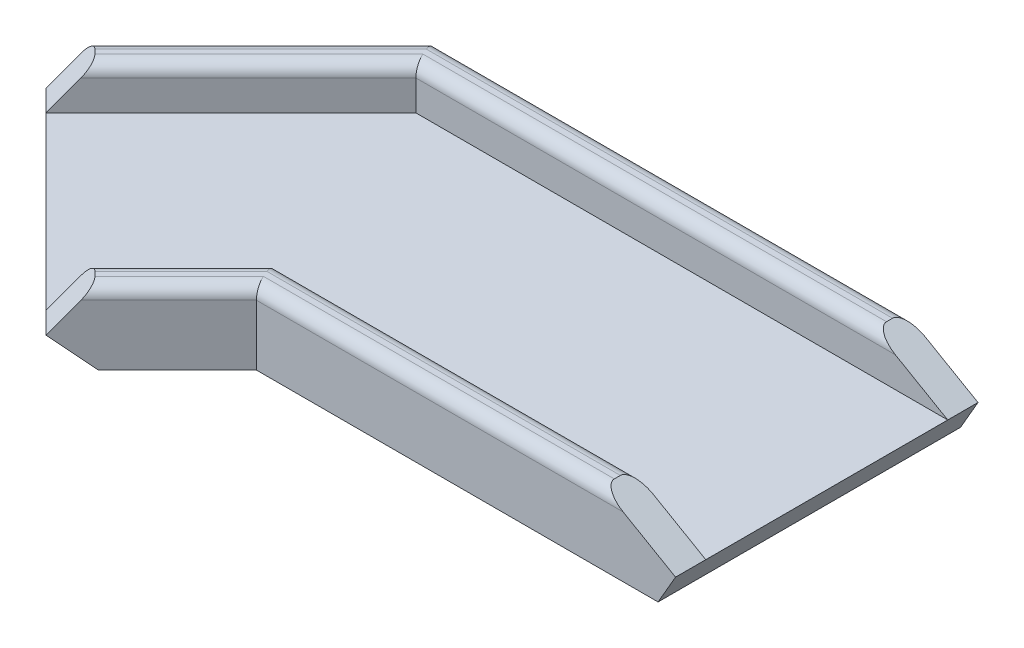
SolidWorks part; units mm, degrees
material "Maple"
ref_plane "Front Plane" through (0, 0, 0) normal (0, 0, 1) x (1, 0, 0)
ref_plane "Top Plane" through (0, 0, 0) normal (0, 1, 0) x (1, 0, 0)
ref_plane "Right Plane" through (0, 0, 0) normal (1, 0, 0) x (0, 0, -1)
sketch "Sketch1" plane through (0, 0, 0) normal (0, 0, 1) x (1, 0, 0)
  line L2 (-57.15, 3.175) -> (57.15, 3.175)
  line L3 (-57.15, 3.175) -> (-57.15, -3.175)
  line L4 (-57.15, -3.175) -> (57.15, -3.175)
  line L5 (57.15, 3.175) -> (57.15, -3.175)
  line L6 (-57.15, 3.175) -> (57.15, -3.175) construction
  line L7 (-57.15, -3.175) -> (57.15, 3.175) construction
  point P1 (0, 0)
  dimension "D1" = 6.35
  dimension "D2" = 114.3
extrude "Boss-Extrude1" add sketch "Sketch1" against normal blind 63.5 contours L5 L2 L4 region at (0, 0, 0)
sketch "Sketch2" plane through (0, 3.175, 0) normal (0, 1, 0) x (1, 0, 0)
  line L1 (57.15, 63.5) -> (-57.15, 63.5)
  line L2 (57.15, 63.5) -> (57.15, 57.15)
  line L3 (57.15, 57.15) -> (-57.15, 57.15)
  line L4 (-57.15, 63.5) -> (-57.15, 57.15)
  line L5 (57.15, 63.5) -> (57.15, 0) construction
  line L6 (-57.15, 0) -> (57.15, 0)
  line L7 (-57.15, 0) -> (-57.15, 6.35)
  line L8 (-57.15, 6.35) -> (57.15, 6.35)
  line L9 (57.15, 0) -> (57.15, 6.35)
  line L10 (-57.15, 63.5) -> (-57.15, 0) construction
  line L11 (-57.15, 0) -> (57.15, 0) construction
  dimension "D1" = 6.35
  dimension "D2" = 6.35
extrude "Boss-Extrude2" add sketch "Sketch2" along normal blind 8.89
sketch "Sketch3" plane through (0, 0, 0) normal (0, 0, 1) x (1, 0, 0)
  line L0 (57.15, 3.175) -> (41.7521, 12.065)
  line L1 (-57.15, 12.065) -> (57.15, 12.065) construction
  line L2 (41.7521, 12.065) -> (48.5274, 23.8003)
  line L3 (48.5274, 23.8003) -> (66.675, 13.3228)
  line L4 (66.675, 13.3228) -> (57.15, -3.175)
  line L5 (-57.15, -3.175) -> (57.15, -3.175) construction
  line L6 (57.15, 3.175) -> (53.4838, -3.175)
  line L7 (-57.15, -3.175) -> (57.15, -3.175) construction
  line L8 (53.4838, -3.175) -> (56.2335, -4.7625)
  line L9 (57.15, 3.175) -> (-57.15, 3.175) construction
  line L10 (56.2335, -4.7625) -> (57.15, -3.175)
  line L11 (57.15, 3.175) -> (-57.15, 3.175) construction
  point P13 (69.85, 18.822)
  point P15 (0, 0)
  point P18 (57.0096, 3.175)
  dimension "D1" = 30
  dimension "D2" = 19.05
extrude "Cut-Extrude1" cut sketch "Sketch3" against normal through all
sketch "Sketch5" plane through (0, 0, 0) normal (0, 1, 0) x (1, 0, 0)
  line L0 (-57.15, 63.5) -> (-30.8474, 0)
  line L2 (-30.8474, 0) -> (-57.15, 0)
  line L3 (-57.15, 0) -> (-57.15, 63.5)
  dimension "D1" = 22.5
extrude "Cut-Extrude2" cut sketch "Sketch5" against normal through all both and the other way through all
sketch "Sketch9" plane through (0, 0, 0) normal (0, 1, 0) x (1, 0, 0)
  line L0 (-30.8474, 0) -> (-57.15, 63.5) construction
  line L1 (-30.8474, 0) -> (-57.15, 63.5)
  line L2 (-57.15, 63.5) -> (-97.8336, 22.8164)
  line L3 (-97.8336, 22.8164) -> (-52.9323, -22.0848)
  line L4 (-52.9323, -22.0848) -> (-30.8474, 0)
  point P6 (0, 0)
  dimension "D1" = 63.5
  dimension "D2" = 112.5
extrude "Boss-Extrude4" add sketch "Sketch9" along normal mid plane 6.35
sketch "Sketch11" plane through (0, 3.175, 0) normal (0, 1, 0) x (1, 0, 0)
  line L0 (-57.15, 63.5) -> (-97.8336, 22.8164)
  line L1 (-97.8336, 22.8164) -> (-93.3434, 18.3263)
  line L2 (-97.8336, 22.8164) -> (-52.9323, -22.0848) construction
  line L3 (-93.3434, 18.3263) -> (-54.5197, 57.15)
  line L4 (-54.5197, 57.15) -> (-57.15, 63.5)
  line L5 (-33.4777, 6.35) -> (-57.4224, -17.5947)
  line L6 (-57.4224, -17.5947) -> (-52.9323, -22.0848)
  line L7 (-52.9323, -22.0848) -> (-30.8474, 0)
  line L8 (-30.8474, 0) -> (-33.4777, 6.35)
extrude "Boss-Extrude5" add sketch "Sketch11" along normal up to surface (8.89 mm away) up to face at (4.7948, 12.065, -3.175)
fillet "Fillet1" radius 2.54 8 edges at (-41.8899, 12.065, 11.0424) (5.4523, 12.065, 0) (4.1372, 12.065, -6.35) (-45.45, 12.065, 5.6224) (-73.9316, 12.065, -37.7382) (-6.3838, 12.065, -57.15)
sketch "Sketch12" plane through (-15.4237, 0, -15.4237) normal (0.7071, 0, 0.7071) x (0.7071, 0, -0.7071)
  line L0 (-53.0451, 3.175) -> (-45.268, -3.175)
  line L1 (-53.0451, 9.525) -> (-53.0451, -3.175) construction
  line L2 (-53.0451, -3.175) -> (-21.8124, -3.175) construction
  line L3 (-45.268, -3.175) -> (-53.3002, -13.0124)
  line L4 (-53.3002, -13.0124) -> (-72.9749, 3.052)
  line L5 (-72.9749, 3.052) -> (-56.9105, 22.7267)
  line L6 (-56.9105, 22.7267) -> (-45.0129, 13.0124)
  line L7 (-45.0129, 13.0124) -> (-53.0451, 3.175)
  line L8 (32.634, 9.525) -> (40.4112, 3.175) construction
  point P6 (0, 0)
  point P11 (-57.7041, 20.6505)
  point P12 (-56.7919, 18.7263)
  dimension "D1" = 12.7
  dimension "D2" = 25.4
  dimension "D3" = 25.4
extrude "Cut-Extrude3" cut sketch "Sketch12" against normal through all
